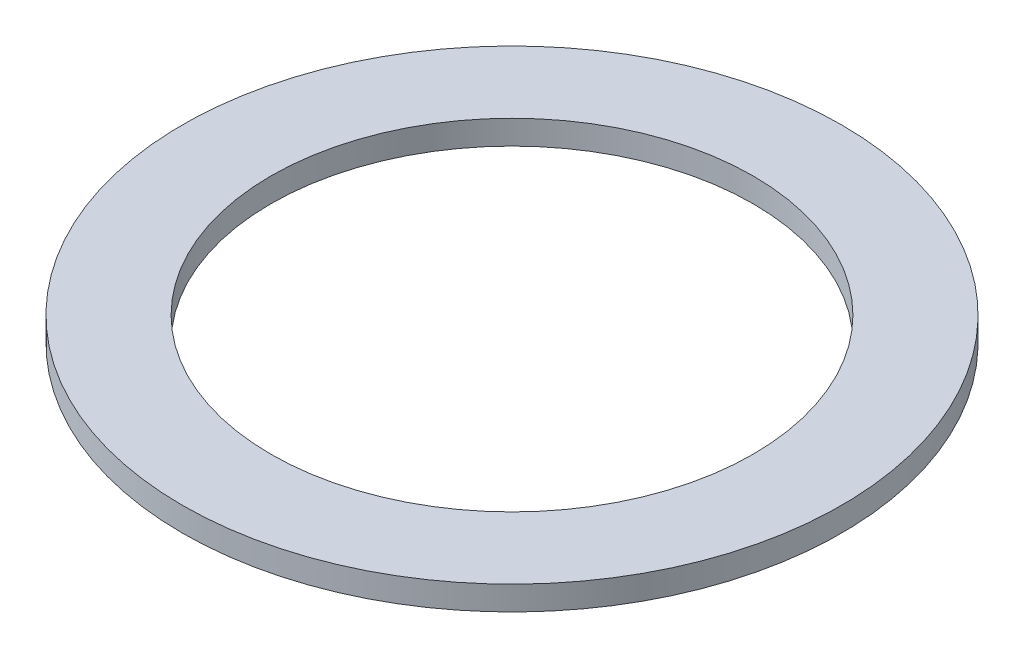
SolidWorks part; units mm, degrees
material "Alum Plate"
ref_plane "Front Plane" through (0, 0, 0) normal (0, 0, 1) x (1, 0, 0)
ref_plane "Top Plane" through (0, 0, 0) normal (0, 1, 0) x (1, 0, 0)
ref_plane "Right Plane" through (0, 0, 0) normal (1, 0, 0) x (0, 0, -1)
other "Bounding Box"
ref_plane "Default Plane" through (-8.9266, -12.7485, 0) normal (-0.1736, 0.9848, 0) x (0.9848, 0.1736, 0)
sketch "Sketch1" plane through (0, 0, 0) normal (0, 1, 0) x (1, 0, 0)
  circle A0 centre (0, 0) radius 12.7
  circle A1 centre (0, 0) radius 17.3609
  dimension "D1" = 25.4
  dimension "D2" = 34.7218
extrude "Boss-Extrude1" add sketch "Sketch1" along normal mid plane 1.27
